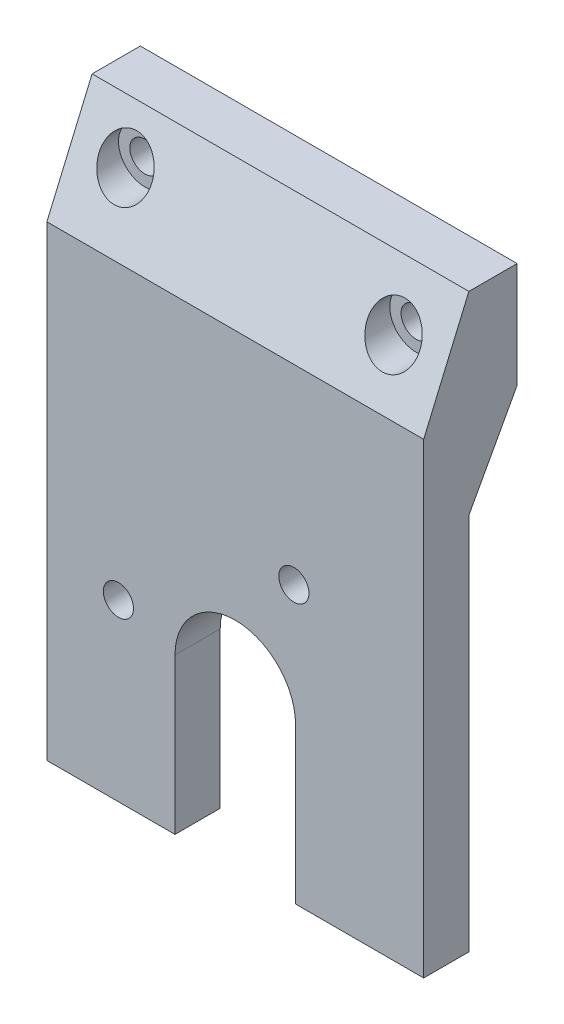
SolidWorks part; units mm, degrees
material "ABS"
ref_plane "Front Plane" through (0, 0, 0) normal (0, 0, 1) x (1, 0, 0)
ref_plane "Top Plane" through (0, 0, 0) normal (0, 1, 0) x (1, 0, 0)
ref_plane "Right Plane" through (0, 0, 0) normal (1, 0, 0) x (0, 0, -1)
sketch "Sketch1" plane through (0, 0, 0) normal (0, 0, 1) x (1, 0, 0)
  line L1 (-37.3941, 10.9555) -> (12.6059, 10.9555)
  line L2 (-37.3941, 10.9555) -> (-37.3941, -7.0445)
  line L3 (-37.3941, -7.0445) -> (12.6059, -7.0445)
  line L4 (12.6059, 10.9555) -> (12.6059, -7.0445)
  dimension "D1" = 50
  dimension "D2" = 18
extrude "Boss-Extrude1" add sketch "Sketch1" along normal blind 7
sketch "Sketch2" plane through (0, 0, 7) normal (0, 0, 1) x (1, 0, 0)
  line L0 (12.6059, -7.0445) -> (12.6059, 10.9555) construction
  line L1 (-37.3941, 10.9555) -> (12.6059, 10.9555)
  line L2 (-37.3941, 10.9555) -> (-37.3941, 2.9555)
  line L3 (-37.3941, 2.9555) -> (12.6059, 2.9555)
  line L4 (12.6059, 10.9555) -> (12.6059, 2.9555)
  dimension "D1" = 8
extrude "Boss-Extrude2" add sketch "Sketch2" along normal blind 6.7
sketch "Sketch3" plane through (12.6059, 0, 0) normal (1, 0, 0) x (0, 0, -1)
  line L0 (-13.7, 10.9555) -> (0, 10.9555) construction
  line L1 (-7, 2.9555) -> (0, 2.9555)
  line L2 (-7, 2.9555) -> (-7, 10.9555)
  line L3 (-7, 10.9555) -> (0, 10.9555)
  line L4 (0, 2.9555) -> (0, 10.9555)
extrude "Boss-Extrude3" add sketch "Sketch3" along normal blind 23
sketch "Sketch4" plane through (-37.3941, 0, 0) normal (-1, 0, 0) x (0, 0, 1)
  line L1 (7, 2.9555) -> (0, 2.9555)
  line L2 (7, 2.9555) -> (7, 10.9555)
  line L3 (7, 10.9555) -> (0, 10.9555)
  line L4 (0, 2.9555) -> (0, 10.9555)
extrude "Boss-Extrude4" add sketch "Sketch4" along normal blind 14
sketch "Sketch5" plane through (0, 0, 7) normal (0, 0, 1) x (1, 0, 0)
  line L1 (-37.3941, -7.0445) -> (12.6059, -7.0445)
  line L2 (-37.3941, -7.0445) -> (-37.3941, 2.9555)
  line L3 (-37.3941, 2.9555) -> (12.6059, 2.9555)
  line L4 (12.6059, -7.0445) -> (12.6059, 2.9555)
extrude "Cut-Extrude1" cut sketch "Sketch5" against normal blind 14
sketch "Sketch6" plane through (0, 0, 7) normal (0, 0, 1) x (1, 0, 0)
  line L0 (35.6059, 10.9555) -> (35.6059, 2.9555) construction
  line L2 (-51.3941, 2.9555) -> (-37.3941, 2.9555) construction
  line L3 (35.6059, 2.9555) -> (12.6059, 2.9555) construction
  circle A0 centre (19.6059, 6.9555) radius 2
  circle A1 centre (28.6059, 6.9555) radius 2
  dimension "D1" = 4
  dimension "D2" = 4
  dimension "D3" = 7
  dimension "D4" = 9
  dimension "D5" = 4
  dimension "D6" = 4
extrude "Cut-Extrude2" cut sketch "Sketch6" against normal blind 14
sketch "Sketch7" plane through (0, 2.9555, 0) normal (0, -1, 0) x (1, 0, 0)
  line L0 (12.6059, 13.7) -> (12.6059, 7) construction
  line L1 (-37.3941, 13.7) -> (12.6059, 13.7)
  line L2 (-37.3941, 13.7) -> (-37.3941, 7.7)
  line L3 (-37.3941, 7.7) -> (12.6059, 7.7)
  line L4 (12.6059, 13.7) -> (12.6059, 7.7)
  dimension "D1" = 6
extrude "Boss-Extrude5" add sketch "Sketch7" along normal blind 67.91
sketch "Sketch8" plane through (0, 0, 13.7) normal (0, 0, 1) x (1, 0, 0)
  line L0 (-12.3941, -44.3312) -> (-12.3941, -64.9545) construction
  line L1 (12.6059, -64.9545) -> (-37.3941, -64.9545) construction
  line L2 (-4.3941, -44.3312) -> (-4.3941, -64.9545)
  line L3 (-20.3941, -44.3312) -> (-20.3941, -64.9545)
  line L4 (-37.3941, 10.9555) -> (-37.3941, -64.9545) construction
  arc A0 (-4.3941, -44.3312) -> (-20.3941, -44.3312) centre (-12.3941, -44.3312) ccw
  arc A1 (-20.3941, -64.9545) -> (-4.3941, -64.9545) centre (-12.3941, -64.9545) ccw
  point P4 (-12.3941, -54.6428)
  dimension "D3" = 20.6233
  dimension "D1" = 16
  dimension "D2" = 25
extrude "Cut-Extrude3" cut sketch "Sketch8" against normal blind 35
sketch "Sketch9" plane through (0, 0, 7.7) normal (0, 0, -1) x (-1, 0, 0)
  line L0 (-12.6059, -64.9545) -> (4.3941, -64.9545) construction
  line L1 (20.3941, -64.9545) -> (37.3941, -64.9545) construction
  circle A0 centre (27.901, -41.7569) radius 2
  circle A1 centre (4.6167, -28.3707) radius 2
  dimension "D1" = 4
  dimension "D2" = 4
  dimension "D3" = 36.5838
  dimension "D4" = 23.1976
extrude "Cut-Extrude5" cut sketch "Sketch9" against normal blind 35
sketch "Sketch13" plane through (0, 0, 7) normal (0, 0, 1) x (1, 0, 0)
  line L1 (-51.3941, 10.9555) -> (-37.3941, 10.9555)
  line L2 (-51.3941, 10.9555) -> (-51.3941, 2.9555)
  line L3 (-51.3941, 2.9555) -> (-37.3941, 2.9555)
  line L4 (-37.3941, 10.9555) -> (-37.3941, 2.9555)
extrude "Cut-Extrude6" cut sketch "Sketch13" against normal blind 10
sketch "Sketch14" plane through (-37.3941, 0, 0) normal (-1, 0, 0) x (0, 0, 1)
  line L1 (7.7, 2.9555) -> (0, 2.9555)
  line L2 (7.7, 2.9555) -> (7.7, 10.9555)
  line L3 (7.7, 10.9555) -> (0, 10.9555)
  line L4 (0, 2.9555) -> (0, 10.9555)
extrude "Cut-Extrude7" cut sketch "Sketch14" against normal blind 120
sketch "Sketch15" plane through (0, 0, 7.7) normal (0, 0, -1) x (-1, 0, 0)
  line L0 (-12.6059, -64.9545) -> (-12.6059, 10.9555) construction
  line L1 (37.3941, 10.9555) -> (-12.6059, 10.9555)
  line L2 (37.3941, 10.9555) -> (37.3941, -3.0445)
  line L3 (37.3941, -3.0445) -> (-12.6059, -3.0445)
  line L4 (-12.6059, 10.9555) -> (-12.6059, -3.0445)
  dimension "D1" = 14
extrude "Boss-Extrude6" add sketch "Sketch15" along normal blind 6.4
sketch "Sketch16" plane through (0, 0, 13.7) normal (0, 0, 1) x (1, 0, 0)
  line L0 (-37.3941, 10.9555) -> (-37.3941, -64.9545) construction
  line L1 (12.6059, 10.9555) -> (-37.3941, 10.9555)
  line L2 (12.6059, 10.9555) -> (12.6059, -3.0445)
  line L3 (12.6059, -3.0445) -> (-37.3941, -3.0445)
  line L4 (-37.3941, 10.9555) -> (-37.3941, -3.0445)
  dimension "D1" = 14
extrude "Cut-Extrude8" cut sketch "Sketch16" against normal up to vertex (6 mm away) up to point (-37.3941, -3.0445, 7.7)
sketch "Sketch17" plane through (-37.3941, 0, 0) normal (-1, 0, 0) x (0, 0, 1)
  line L0 (13.7, -3.0445) -> (7.7, -3.0445)
  line L1 (7.7, -3.0445) -> (7.7, 10.9555)
  line L2 (7.7, 10.9555) -> (13.7, -3.0445)
  line L3 (7.7, -3.0445) -> (1.3, -3.0445)
  line L4 (1.3, -3.0445) -> (7.7, -3.0445) construction
  line L5 (1.3, -3.0445) -> (7.7, -14.7804)
  line L6 (7.7, -64.9545) -> (7.7, -3.0445) construction
  line L7 (7.7, -14.7804) -> (7.7, -3.0445)
  line M1 (1.3, -3.0445) -> (7.7, -3.0445)
  line M2 (7.7, -3.0445) -> (7.7, 10.9555)
extrude "Boss-Extrude7" add sketch "Sketch17" against normal blind 50 contours L2 L0 M2 | L5 L7 M1 region at (-37.3941, -6.9565, 5.5667) region at (-37.3941, 1.6222, 9.7)
sketch "Sketch18" plane through (0, 0, 1.3) normal (0, 0, -1) x (-1, 0, 0)
  line L0 (-12.6059, 10.9555) -> (-12.6059, -3.0445) construction
  line L1 (37.3941, 10.9555) -> (-12.6059, 10.9555) construction
  circle A0 centre (-5.6059, 3.9555) radius 2
  circle A1 centre (30.3941, 4.9553) radius 2
  dimension "D1" = 4
  dimension "D2" = 4
  dimension "D3" = 36
  dimension "D4" = 7
  dimension "D5" = 7
extrude "Cut-Extrude9" cut sketch "Sketch18" against normal blind 6.4
sketch "Sketch19" plane through (0, 0, 7.7) normal (0, 0, -1) x (-1, 0, 0)
  circle A0 centre (30.3941, 4.9553) radius 3.5
  circle A1 centre (-5.6059, 3.9555) radius 3.5
  dimension "D1" = 7
  dimension "D2" = 7
extrude "Cut-Extrude10" cut sketch "Sketch19" against normal blind 6.4
